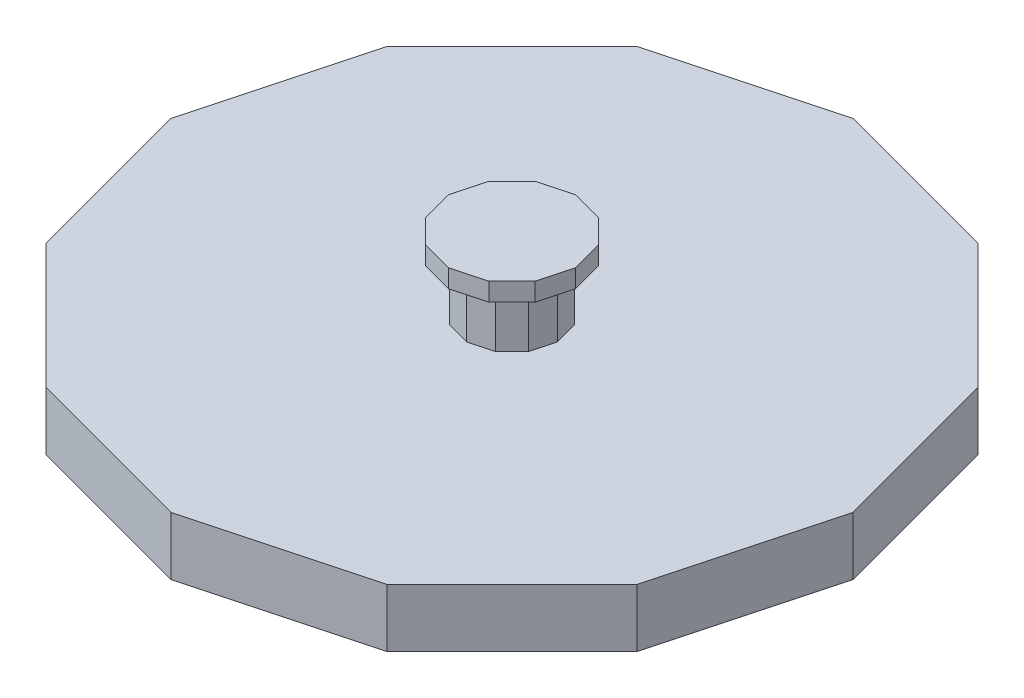
SolidWorks part; units mm, degrees
ref_plane "Front Plane" through (0, 0, 0) normal (0, 0, 1) x (1, 0, 0)
ref_plane "Top Plane" through (0, 0, 0) normal (0, 1, 0) x (1, 0, 0)
ref_plane "Right Plane" through (0, 0, 0) normal (1, 0, 0) x (0, 0, -1)
sketch "Sketch1" plane through (0, 0, 0) normal (0, 1, 0) x (1, 0, 0)
  line L1 (0, 187.3896) -> (-93.6948, 162.2842)
  line L2 (-93.6948, 162.2842) -> (-162.2842, 93.6948)
  line L3 (-162.2842, 93.6948) -> (-187.3896, 0)
  line L4 (-187.3896, 0) -> (-162.2842, -93.6948)
  line L5 (-162.2842, -93.6948) -> (-93.6948, -162.2842)
  line L6 (-93.6948, -162.2842) -> (0, -187.3896)
  line L7 (0, -187.3896) -> (93.6948, -162.2842)
  line L8 (93.6948, -162.2842) -> (162.2842, -93.6948)
  line L9 (162.2842, -93.6948) -> (187.3896, 0)
  line L10 (187.3896, 0) -> (162.2842, 93.6948)
  line L11 (162.2842, 93.6948) -> (93.6948, 162.2842)
  line L12 (93.6948, 162.2842) -> (0, 187.3896)
  circle A0 centre (0, 0) radius 181.0045 construction
  dimension "D1" = 97
extrude "Boss-Extrude1" add sketch "Sketch1" along normal blind 2
sketch "Sketch2" plane through (0, 0, 0) normal (0, -1, 0) x (1, 0, 0)
  line L1 (0, 187.3896) -> (-93.6948, 162.2842)
  line L2 (-93.6948, 162.2842) -> (-162.2842, 93.6948)
  line L3 (-162.2842, 93.6948) -> (-187.3896, 0)
  line L4 (-187.3896, 0) -> (-162.2842, -93.6948)
  line L5 (-162.2842, -93.6948) -> (-93.6948, -162.2842)
  line L6 (-93.6948, -162.2842) -> (0, -187.3896)
  line L7 (0, -187.3896) -> (93.6948, -162.2842)
  line L8 (93.6948, -162.2842) -> (162.2842, -93.6948)
  line L9 (162.2842, -93.6948) -> (187.3896, 0)
  line L10 (187.3896, 0) -> (162.2842, 93.6948)
  line L11 (162.2842, 93.6948) -> (93.6948, 162.2842)
  line L12 (93.6948, 162.2842) -> (0, 187.3896)
  line L13 (0, 185.3191) -> (-92.6595, 160.491)
  line L14 (-92.6595, 160.491) -> (-160.491, 92.6595)
  line L15 (-160.491, 92.6595) -> (-185.3191, 0)
  line L16 (-185.3191, 0) -> (-160.491, -92.6595)
  line L17 (-160.491, -92.6595) -> (-92.6595, -160.491)
  line L18 (-92.6595, -160.491) -> (0, -185.3191)
  line L19 (0, -185.3191) -> (92.6595, -160.491)
  line L20 (92.6595, -160.491) -> (160.491, -92.6595)
  line L21 (160.491, -92.6595) -> (185.3191, 0)
  line L22 (185.3191, 0) -> (160.491, 92.6595)
  line L23 (160.491, 92.6595) -> (92.6595, 160.491)
  line L24 (92.6595, 160.491) -> (0, 185.3191)
  circle A0 centre (0, 0) radius 181.0045 construction
  circle A1 centre (0, 0) radius 179.0045 construction
  dimension "D1" = 97
  dimension "D2" = 2
extrude "Boss-Extrude2" add sketch "Sketch2" along normal blind 30
sketch "Sketch3" plane through (0, 2, 0) normal (0, 1, 0) x (1, 0, 0)
  line L1 (0, 25.1141) -> (-12.557, 21.7494)
  line L2 (-12.557, 21.7494) -> (-21.7494, 12.557)
  line L3 (-21.7494, 12.557) -> (-25.1141, 0)
  line L4 (-25.1141, 0) -> (-21.7494, -12.557)
  line L5 (-21.7494, -12.557) -> (-12.557, -21.7494)
  line L6 (-12.557, -21.7494) -> (0, -25.1141)
  line L7 (0, -25.1141) -> (12.557, -21.7494)
  line L8 (12.557, -21.7494) -> (21.7494, -12.557)
  line L9 (21.7494, -12.557) -> (25.1141, 0)
  line L10 (25.1141, 0) -> (21.7494, 12.557)
  line L11 (21.7494, 12.557) -> (12.557, 21.7494)
  line L12 (12.557, 21.7494) -> (0, 25.1141)
  line L13 (0, 23.0435) -> (-11.5218, 19.9563)
  line L14 (-11.5218, 19.9563) -> (-19.9563, 11.5218)
  line L15 (-19.9563, 11.5218) -> (-23.0435, 0)
  line L16 (-23.0435, 0) -> (-19.9563, -11.5218)
  line L17 (-19.9563, -11.5218) -> (-11.5218, -19.9563)
  line L18 (-11.5218, -19.9563) -> (0, -23.0435)
  line L19 (0, -23.0435) -> (11.5218, -19.9563)
  line L20 (11.5218, -19.9563) -> (19.9563, -11.5218)
  line L21 (19.9563, -11.5218) -> (23.0435, 0)
  line L22 (23.0435, 0) -> (19.9563, 11.5218)
  line L23 (19.9563, 11.5218) -> (11.5218, 19.9563)
  line L24 (11.5218, 19.9563) -> (0, 23.0435)
  circle A2 centre (0, 0) radius 24.2583 construction
  circle A3 centre (0, 0) radius 22.2583 construction
  dimension "D1" = 13
  dimension "D2" = 2
extrude "Boss-Extrude3" add sketch "Sketch3" along normal blind 30
extrude "Boss-Extrude4" add sketch "Sketch3<2>" along normal blind 30
sketch "Sketch3<2>" plane through (0, 2, 0) normal (0, 1, 0) x (1, 0, 0) same geometry as "Sketch3"
sketch "Sketch5" plane through (0, 32, 0) normal (0, 1, 0) x (1, 0, 0)
  line L1 (0, 34.7733) -> (-17.3867, 30.1146)
  line L2 (-17.3867, 30.1146) -> (-30.1146, 17.3867)
  line L3 (-30.1146, 17.3867) -> (-34.7733, 0)
  line L4 (-34.7733, 0) -> (-30.1146, -17.3867)
  line L5 (-30.1146, -17.3867) -> (-17.3867, -30.1146)
  line L6 (-17.3867, -30.1146) -> (0, -34.7733)
  line L7 (0, -34.7733) -> (17.3867, -30.1146)
  line L8 (17.3867, -30.1146) -> (30.1146, -17.3867)
  line L9 (30.1146, -17.3867) -> (34.7733, 0)
  line L10 (34.7733, 0) -> (30.1146, 17.3867)
  line L11 (30.1146, 17.3867) -> (17.3867, 30.1146)
  line L12 (17.3867, 30.1146) -> (0, 34.7733)
  circle A0 centre (0, 0) radius 33.5885 construction
  dimension "D1" = 18
extrude "Boss-Extrude5" add sketch "Sketch5" along normal blind 10
